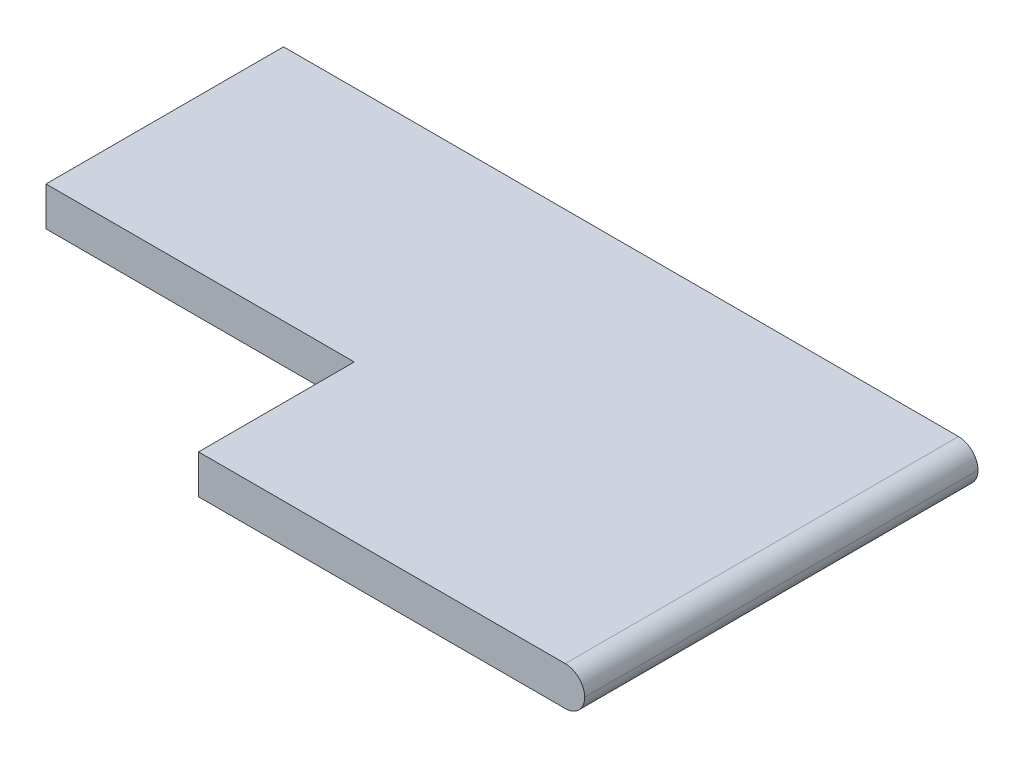
SolidWorks part; units mm, degrees
ref_plane "Front Plane" through (0, 0, 0) normal (0, 0, 1) x (1, 0, 0)
ref_plane "Top Plane" through (0, 0, 0) normal (0, 1, 0) x (1, 0, 0)
ref_plane "Right Plane" through (0, 0, 0) normal (1, 0, 0) x (0, 0, -1)
other "Center of Mass"
ref_plane "Plane2" through (0, 0, 30.3) normal (0, 0, 1) x (1, 0, 0)
sketch "Sketch1" plane through (0, 0, 0) normal (0, 0, 1) x (1, 0, 0)
  line L1 (-4.25, 1.5) -> (49.25, 1.5)
  line L2 (-4.25, 1.5) -> (-4.25, -1.5)
  line L3 (-4.25, -1.5) -> (49.25, -1.5)
  line L4 (49.25, 1.5) -> (49.25, -1.5)
  point P4 (49.25, 0)
  point P6 (0, 0)
  dimension "D1" = 53.5
  dimension "D2" = 4.25
  dimension "D3" = 3
extrude "Boss-Extrude1" add sketch "Sketch1" along normal up to surface (30.3 mm away) contours L4 L1 L3 | L2 L3 L1 region at (22.5, 0, 0) up to plane "Plane2"
sketch "Sketch2" plane through (0, 0, 30.3) normal (0, 0, 1) x (1, 0, 0)
  line L0 (-4.25, -1.5) -> (49.25, -1.5) construction
  line L1 (-4.25, 1.5) -> (19.5, 1.5)
  line L2 (-4.25, 1.5) -> (-4.25, -1.5)
  line L3 (-4.25, -1.5) -> (19.5, -1.5)
  line L4 (19.5, 1.5) -> (19.5, -1.5)
  line L5 (49.25, 1.5) -> (49.25, -1.5) construction
  dimension "D1" = 29.75
extrude "Cut-Extrude1" cut sketch "Sketch2" against normal blind 12
fillet "Fillet1" radius 1.5 2 edges at (49.25, -1.5, 15.15) (49.25, 1.5, 15.15)
ref_axis "Axis1" through (0, 0, -7.6722) along (0, 0, 1)
